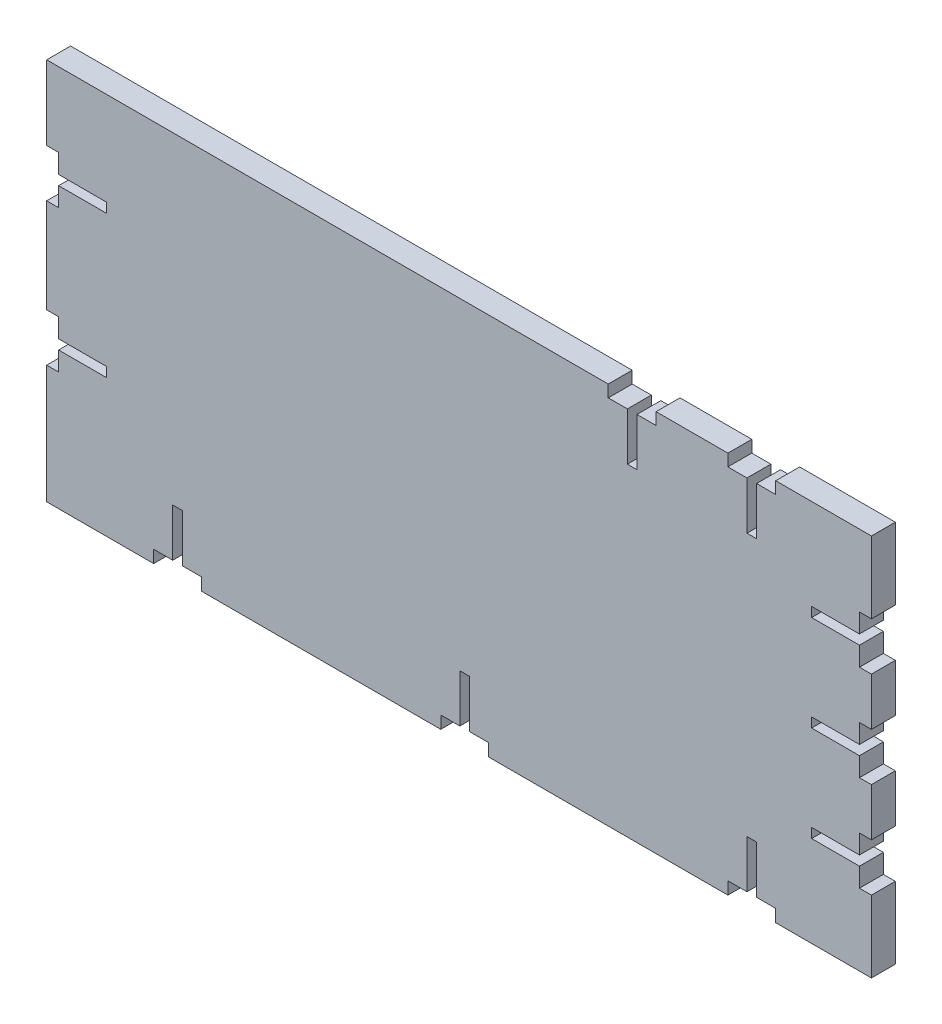
SolidWorks part; units mm, degrees
ref_plane "Front Plane" through (0, 0, 0) normal (0, 0, 1) x (1, 0, 0)
ref_plane "Top Plane" through (0, 0, 0) normal (0, 1, 0) x (1, 0, 0)
ref_plane "Right Plane" through (0, 0, 0) normal (1, 0, 0) x (0, 0, -1)
sketch "Sketch1" plane through (0, 0, 0) normal (0, 0, 1) x (1, 0, 0)
  line L0 (0, 0) -> (127, 0)
  line L1 (127, 0) -> (127, 101.6)
  line L3 (0, 101.6) -> (0, 0) construction
  line L4 (0, 101.6) -> (-70.6924, 172.2924)
  line L5 (-70.6924, 172.2924) -> (-91.8969, 151.088)
  line L6 (-91.8969, 151.088) -> (-91.8969, 0)
  line L7 (-91.8969, 0) -> (0, 0)
  line L8 (127, 101.6) -> (0, 101.6)
  dimension "D1" = 127
  dimension "D2" = 101.6
  dimension "D3" = 135
  dimension "D4" = 29.9876
  dimension "D5" = 151.088
extrude "Boss-Extrude1" add sketch "Sketch1" along normal blind 6.35
sketch "Sketch2" plane through (0, 0, 0) normal (0, 0, -1) x (-1, 0, 0)
  line L0 (0, 101.6) -> (-25.4, 101.6) construction
  line L1 (-127, 101.6) -> (0, 101.6) construction
  line L2 (-25.4, 101.6) -> (-31.75, 101.6)
  line L3 (-25.4, 101.6) -> (-61.321, 65.679)
  line L4 (-31.75, 101.6) -> (-67.671, 65.679)
  line L5 (-67.671, 65.679) -> (-61.321, 65.679)
  line L6 (-49.7105, 83.6395) -> (-43.3605, 83.6395) construction
  line L7 (-31.75, 101.6) -> (-49.7105, 83.6395)
  dimension "D1" = 25.4
  dimension "D2" = 6.35
  dimension "D3" = 50.8
  dimension "D4" = 45
  dimension "D5" = 45
  dimension "D6" = 50.8
  dimension "D7" = 135
  dimension "D8" = 25.4
sketch "Sketch3" plane through (0, 0, 0) normal (0, 0, -1) x (-1, 0, 0)
  line L0 (70.6924, 172.2924) -> (61.7122, 163.3122) construction
  line L1 (0, 101.6) -> (70.6924, 172.2924) construction
  line L2 (59.4671, 161.0671) -> (63.9572, 165.5572)
  line L3 (59.4671, 161.0671) -> (63.9572, 156.577) construction
  line L5 (68.4474, 161.0671) -> (63.9572, 165.5572) construction
  line L6 (70.6924, 172.2924) -> (91.8969, 151.088) construction
  line L7 (63.9572, 156.577) -> (68.4474, 161.0671)
  line L8 (63.9572, 156.577) -> (66.2023, 154.3319)
  line L9 (68.4474, 161.0671) -> (70.6924, 158.822)
  line L10 (70.6924, 158.822) -> (66.2023, 154.3319)
  line L11 (-127, 25.4) -> (-127, 0)
  line L12 (-127, 50.8) -> (-127, 101.6) construction
  line L13 (-127, 0) -> (-127, 50.8) construction
  line L14 (-25.4, 0) -> (-12.7, 0)
  line L15 (-127, 82.55) -> (-127, 69.85)
  line L16 (0, 101.6) -> (-63.5, 101.6) construction
  line L17 (-127, 44.45) -> (-127, 57.15)
  line L18 (-127, 19.05) -> (-127, 31.75)
  line L19 (-63.5, 101.6) -> (-127, 101.6) construction
  line L20 (-101.6, 101.6) -> (-88.9, 101.6)
  line L21 (-69.85, 101.6) -> (-57.15, 101.6)
  line L22 (70.6924, 172.2924) -> (0, 101.6) construction
  line L23 (30.8561, 132.4561) -> (39.8363, 141.4363)
  line L24 (91.8969, 119.666) -> (91.8969, 106.966)
  line L25 (91.8969, 0) -> (91.8969, 75.544) construction
  line L26 (91.8969, 75.544) -> (91.8969, 151.088) construction
  line L27 (91.8969, 81.894) -> (91.8969, 69.194)
  line L28 (91.8969, 44.122) -> (91.8969, 31.422)
  line L29 (30.8561, 132.4561) -> (33.1011, 130.211)
  line L30 (-127, 82.55) -> (-123.825, 82.55)
  line L31 (-127, 82.55) -> (-127, 69.85)
  line L32 (-127, 69.85) -> (-123.825, 69.85)
  line L33 (-123.825, 82.55) -> (-123.825, 69.85) construction
  line L34 (-127, 57.15) -> (-123.825, 57.15)
  line L35 (-127, 57.15) -> (-127, 44.45)
  line L36 (-127, 44.45) -> (-123.825, 44.45)
  line L37 (-123.825, 57.15) -> (-123.825, 44.45) construction
  line L38 (-127, 31.75) -> (-123.825, 31.75)
  line L39 (-127, 31.75) -> (-127, 19.05)
  line L40 (-127, 19.05) -> (-123.825, 19.05)
  line L41 (-123.825, 31.75) -> (-123.825, 19.05) construction
  line L42 (-101.6, 101.6) -> (-88.9, 101.6)
  line L43 (-101.6, 101.6) -> (-101.6, 98.425)
  line L44 (-101.6, 98.425) -> (-88.9, 98.425) construction
  line L45 (-88.9, 101.6) -> (-88.9, 98.425)
  line L46 (-69.85, 101.6) -> (-57.15, 101.6)
  line L47 (-69.85, 101.6) -> (-69.85, 98.425)
  line L48 (-69.85, 98.425) -> (-57.15, 98.425) construction
  line L49 (-57.15, 101.6) -> (-57.15, 98.425)
  line L54 (39.8363, 141.4363) -> (42.0814, 139.1913)
  line L55 (42.0814, 139.1913) -> (33.1011, 130.211)
  line L56 (-123.825, 77.4827) -> (-123.825, 74.9173) construction
  line L57 (91.8969, 119.666) -> (88.7219, 119.666)
  line L58 (91.8969, 119.666) -> (91.8969, 106.966)
  line L59 (91.8969, 106.966) -> (88.7219, 106.966)
  line L60 (88.7219, 119.666) -> (88.7219, 106.966) construction
  line L61 (91.8969, 81.894) -> (88.7219, 81.894)
  line L62 (91.8969, 81.894) -> (91.8969, 69.194)
  line L63 (91.8969, 69.194) -> (88.7219, 69.194)
  line L64 (88.7219, 81.894) -> (88.7219, 69.194) construction
  line L65 (91.8969, 44.122) -> (88.7219, 44.122)
  line L66 (91.8969, 44.122) -> (91.8969, 31.422)
  line L67 (91.8969, 31.422) -> (88.7219, 31.422)
  line L68 (88.7219, 44.122) -> (88.7219, 31.422) construction
  line L69 (-101.6, 0) -> (-101.6, 3.302)
  line L70 (-123.825, 77.4827) -> (-111.125, 77.4827)
  line L71 (-123.825, 77.4827) -> (-123.825, 74.9173) construction
  line L72 (-123.825, 74.9173) -> (-111.125, 74.9173)
  line L73 (-111.125, 77.4827) -> (-111.125, 74.9173)
  line L74 (91.8969, 0) -> (-127, 0) construction
  line L75 (-101.6, 3.302) -> (-88.9, 3.302) construction
  line L76 (-88.9, 3.302) -> (-88.9, 0)
  line L77 (-101.6, 0) -> (-88.9, 0)
  line L78 (-25.4, 0) -> (-25.4, 3.302)
  line L79 (-25.4, 3.302) -> (-12.7, 3.302) construction
  line L80 (-12.7, 3.302) -> (-12.7, 0)
  line L81 (50.8, 0) -> (50.8, 3.302)
  line L82 (50.8, 3.302) -> (63.5, 3.302) construction
  line L83 (63.5, 3.302) -> (63.5, 0)
  line L84 (63.5, 0) -> (50.8, 0)
  line L85 (-93.9673, 3.302) -> (-96.5327, 3.302) construction
  line L86 (-96.5327, 3.302) -> (-96.5327, 16.002)
  line L87 (-96.5327, 16.002) -> (-93.9673, 16.002)
  line L88 (-93.9673, 16.002) -> (-93.9673, 3.302)
  line L89 (-17.7673, 3.302) -> (-20.3327, 3.302) construction
  line L90 (-20.3327, 3.302) -> (-20.3327, 16.002)
  line L91 (-20.3327, 16.002) -> (-17.7673, 16.002)
  line L92 (-17.7673, 16.002) -> (-17.7673, 3.302)
  line L93 (58.4327, 3.302) -> (55.8673, 3.302) construction
  line L94 (55.8673, 3.302) -> (55.8673, 16.002)
  line L95 (55.8673, 16.002) -> (58.4327, 16.002)
  line L96 (58.4327, 16.002) -> (58.4327, 3.302)
  line L97 (-123.825, 24.1173) -> (-123.825, 26.6827) construction
  line L98 (-123.825, 26.6827) -> (-111.125, 26.6827)
  line L99 (-111.125, 26.6827) -> (-111.125, 24.1173)
  line L100 (-111.125, 24.1173) -> (-123.825, 24.1173)
  line L101 (-123.825, 49.5173) -> (-123.825, 52.0827) construction
  line L102 (-123.825, 52.0827) -> (-111.125, 52.0827)
  line L103 (-111.125, 52.0827) -> (-111.125, 49.5173)
  line L104 (-111.125, 49.5173) -> (-123.825, 49.5173)
  line L105 (-93.9673, 98.425) -> (-96.5327, 98.425) construction
  line L106 (-96.5327, 98.425) -> (-96.5327, 85.725)
  line L107 (-96.5327, 85.725) -> (-93.9673, 85.725)
  line L108 (-93.9673, 85.725) -> (-93.9673, 98.425)
  line L109 (-62.23, 98.425) -> (-64.77, 98.425) construction
  line L110 (-64.77, 98.425) -> (-64.77, 85.725)
  line L111 (-64.77, 85.725) -> (-62.23, 85.725)
  line L112 (-62.23, 85.725) -> (-62.23, 98.425)
  line L113 (88.7219, 112.0333) -> (88.7219, 114.5987) construction
  line L114 (88.7219, 114.5987) -> (76.0219, 114.5987)
  line L115 (76.0219, 114.5987) -> (76.0219, 112.0333)
  line L116 (76.0219, 112.0333) -> (88.7219, 112.0333)
  line L117 (88.7219, 74.2613) -> (88.7219, 76.8267) construction
  line L118 (88.7219, 76.8267) -> (76.0219, 76.8267)
  line L119 (76.0219, 76.8267) -> (76.0219, 74.2613)
  line L120 (76.0219, 74.2613) -> (88.7219, 74.2613)
  line L121 (88.7219, 36.4893) -> (88.7219, 39.0547) construction
  line L122 (88.7219, 39.0547) -> (76.0219, 39.0547)
  line L123 (76.0219, 39.0547) -> (76.0219, 36.4893)
  line L124 (76.0219, 36.4893) -> (88.7219, 36.4893)
  line L125 (-123.825, 44.45) -> (-123.825, 49.5173)
  line L126 (-123.825, 52.0827) -> (-123.825, 57.15) construction
  line L127 (-123.825, 82.55) -> (-123.825, 77.4827)
  line L128 (-123.825, 74.9173) -> (-123.825, 69.85)
  line L129 (-123.825, 57.15) -> (-123.825, 52.0827)
  line L130 (-123.825, 52.0827) -> (-123.825, 57.15)
  line L131 (-123.825, 26.6827) -> (-123.825, 31.75)
  line L132 (-123.825, 19.05) -> (-123.825, 24.1173)
  line L133 (-101.6, 3.302) -> (-96.5327, 3.302)
  line L135 (-101.6, 98.425) -> (-96.5327, 98.425)
  line L136 (-93.9673, 98.425) -> (-88.9, 98.425)
  line L137 (-64.77, 98.425) -> (-69.85, 98.425)
  line L138 (-62.23, 98.425) -> (-57.15, 98.425)
  line L139 (-93.9673, 3.302) -> (-88.9, 3.302)
  line L140 (-25.4, 3.302) -> (-20.3327, 3.302)
  line L141 (-17.7673, 3.302) -> (-12.7, 3.302)
  line L142 (50.8, 3.302) -> (55.8673, 3.302)
  line L143 (58.4327, 3.302) -> (63.5, 3.302)
  line L144 (88.7219, 39.0547) -> (88.7219, 44.122)
  line L145 (88.7219, 31.422) -> (88.7219, 36.4893)
  line L146 (88.7219, 69.194) -> (88.7219, 74.2613)
  line L147 (88.7219, 76.8267) -> (88.7219, 81.894)
  line L148 (88.7219, 106.966) -> (88.7219, 112.0333)
  line L149 (88.7219, 114.5987) -> (88.7219, 119.666)
  point P8 (61.7122, 163.3122)
  point P27 (-127, 76.2)
  point P30 (-127, 50.8)
  point P33 (-127, 25.4)
  point P34 (-95.25, 101.6)
  point P36 (-95.25, 101.6)
  point P39 (-63.5, 85.725)
  point P41 (-31.75, 101.6)
  point P42 (-63.5, 101.6)
  point P45 (35.3462, 136.9462)
  point P53 (91.8969, 113.316)
  point P56 (91.8969, 75.544)
  point P59 (91.8969, 37.772)
  point P70 (-95.25, 3.302)
  point P82 (-123.825, 76.2)
  point P102 (-19.05, 3.302)
  point P107 (57.15, 3.302)
  point P112 (-123.825, 25.4)
  point P117 (-123.825, 50.8)
  point P122 (-95.25, 98.425)
  point P127 (-63.5, 98.425)
  point P132 (88.7219, 113.316)
  point P137 (88.7219, 75.544)
  point P142 (88.7219, 37.772)
  line M40 (-127, 0) -> (91.8969, 0)
  line M41 (91.8969, 0) -> (91.8969, 151.088)
  line M44 (0, 101.6) -> (-127, 101.6)
  line M45 (-127, 101.6) -> (-127, 0)
  dimension "D1" = 12.7
  dimension "D2" = 9.525
  dimension "D3" = 6.35
  dimension "D4" = 6.35
  dimension "D5" = 6.35
  dimension "D6" = 3.175
  dimension "D7" = 3.175
  dimension "D8" = 12.7
  dimension "D9" = 12.7
  dimension "D10" = 12.7
  dimension "D11" = 25.4
  dimension "D12" = 12.7
  dimension "D13" = 12.7
  dimension "D14" = 12.7
  dimension "D15" = 31.75
  dimension "D16" = 12.7
  dimension "D17" = 75.544
  dimension "D18" = 12.7
  dimension "D19" = 12.7
  dimension "D20" = 12.7
  dimension "D21" = 3.175
  dimension "D22" = 3.175
  dimension "D23" = 3.175
  dimension "D24" = 3.175
  dimension "D25" = 3.175
  dimension "D26" = 3.302
  dimension "D27" = 3.175
  dimension "D28" = 3.175
  dimension "D29" = 12.7
  dimension "D30" = 3.175
  dimension "D31" = 3.175
  dimension "D32" = 3.175
  dimension "D33" = 2.5654
  dimension "D34" = 12.7
  dimension "D35" = 25.4
  dimension "D36" = 63.5
  dimension "D37" = 63.5
  dimension "D38" = 3.302
  dimension "D39" = 12.7
  dimension "D40" = 12.7
  dimension "D41" = 3.302
  dimension "D42" = 2.5654
  dimension "D43" = 12.7
  dimension "D44" = 12.7
  dimension "D45" = 2.5654
  dimension "D46" = 12.7
  dimension "D47" = 2.5654
  dimension "D48" = 12.7
  dimension "D49" = 2.5654
  dimension "D50" = 12.7
  dimension "D51" = 1.27
  dimension "D52" = 12.7
  dimension "D53" = 2.5654
  dimension "D54" = 2.5654
  dimension "D55" = 12.7
  dimension "D56" = 2.5654
  dimension "D57" = 12.7
  dimension "D58" = 12.7
  dimension "D59" = 2.5654
  dimension "D60" = 12.7
  dimension "D61" = 2.5654
extrude "Cut-Extrude4" cut sketch "Sketch3" against normal blind 127 and the other way blind 127 contours L108 L136 L45 L43 L135 L106 L107 M44 | L112 L138 L49 L47 L137 L110 L111 M44 | L128 L72 L73 L70 L127 L30 L32 M45 | L129 L34 L36 L125 L104 L103 L102 M45 | L40 L132 L100 L99 L98 L131 L38 M45 | L139 L88 L87 L86 L133 L69 L76 M40 | L141 L92 L91 L90 L140 L78 L80 M40 | L143 L96 L95 L94 L142 L81 L83 M40 | L145 L67 L65 L144 L122 L123 L124 M41 | L147 L118 L119 L120 L146 L63 L61 M41 | L149 L114 L115 L116 L148 L59 L57 M41 | L10 L9 L7 L8 region at (-67.3248, 157.6995, 0) region at (121.8652, 25.4, 0) region at (63.5, 96.4847, 0) region at (95.25, 96.4652, 0) region at (121.8652, 76.2, 0) region at (121.8652, 50.8, 0) region at (-86.7621, 113.316, 0) region at (-86.7621, 75.544, 0) region at (-86.7621, 37.772, 0) region at (-57.15, 5.1493, 0) region at (19.05, 5.1493, 0) region at (95.25, 5.1493, 0)
sketch "Sketch4" plane through (0, 0, 0) normal (0, 0, 1) x (1, 0, 0)
  line L0 (-81.9177, 147.5967) -> (-79.6727, 149.8418)
  line L1 (-81.9177, 147.5967) -> (-77.4276, 143.1066)
  line L2 (-77.4276, 143.1066) -> (-75.1826, 145.3517)
  line L3 (-75.1826, 145.3517) -> (-79.6727, 149.8418)
  line L5 (-70.6924, 158.822) -> (-66.2023, 154.3319) construction
  line L6 (-70.6924, 172.2924) -> (-91.8969, 151.088) construction
  dimension "D1" = 3.175
  dimension "D2" = 6.35
  dimension "D3" = 12.7
  dimension "D4" = 9.525
extrude "Cut-Extrude5" cut sketch "Sketch4" against normal blind 127 and the other way blind 127 contours L0 L3 L2 L1
sketch "Sketch5" plane through (0, 0, 0) normal (0, 0, 1) x (1, 0, 0)
  line L1 (127, 101.6) -> (-102.8084, 101.6)
  line L2 (127, 101.6) -> (127, 179.517)
  line L3 (127, 179.517) -> (-102.8084, 179.517)
  line L4 (-102.8084, 101.6) -> (-102.8084, 179.517)
extrude "Cut-Extrude7" cut sketch "Sketch5" against normal blind 127 and the other way blind 127
